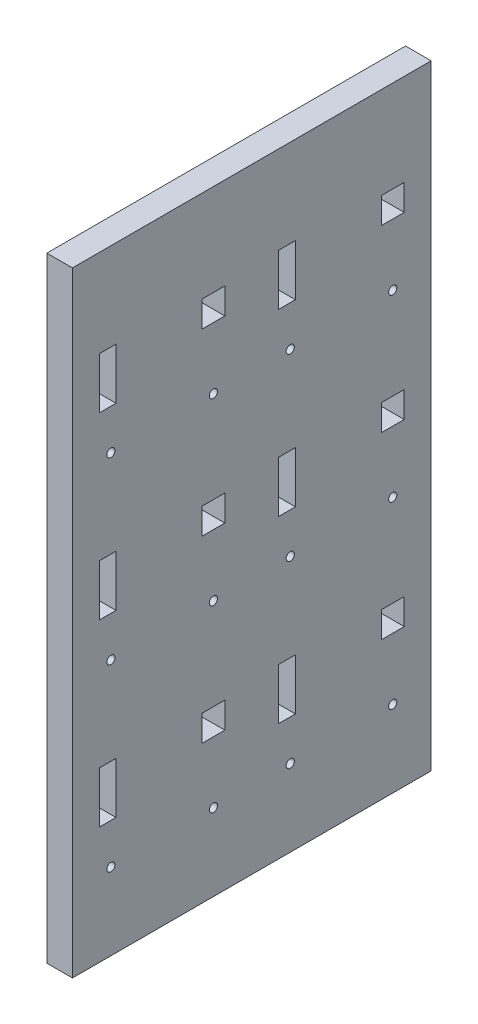
SolidWorks part; units mm, degrees
ref_plane "Alzado" through (0, 0, 0) normal (1, 0, 0) x (0, 1, 0)
ref_plane "Planta" through (0, 0, 0) normal (0, 0, 1) x (0, 1, 0)
ref_plane "Vista lateral" through (0, 0, 0) normal (0, 1, 0) x (-1, 0, 0)
sketch "Croquis2" plane through (0, 0, 0) normal (1, 0, 0) x (0, 1, 0)
  line L1 (0, 0) -> (240, 0)
  line L2 (0, 0) -> (0, 140)
  line L3 (0, 140) -> (240, 140)
  line L4 (240, 0) -> (240, 140)
  dimension "D1" = 240
  dimension "D2" = 140
extrude "Saliente-Extruir1" add sketch "Croquis2" along normal blind 10
sketch "Croquis3" plane through (10, 0, 0) normal (1, 0, 0) x (0, 1, 0)
  line L0 (240, 0) -> (240, 140) construction
  line L1 (0, 140) -> (0, 0) construction
  line L2 (0, 0) -> (240, 0) construction
  line L3 (240, 0) -> (240, 140) construction
  line L4 (0, 140) -> (0, 0) construction
  line L5 (0, 0) -> (240, 0)
  line L6 (85, 154.7761) -> (85, -24.7939) construction
  line L7 (155, 154.7761) -> (155, -26.7975) construction
  line L12 (15, 154.7761) -> (15, -24.7939) construction
  line L13 (225, 154.7761) -> (225, -26.7975) construction
  line L14 (155, -10.8706) -> (225, -10.8706) construction
  line L15 (120, -173.0582) -> (120, 151.3171) construction
  line L16 (15, -10.8706) -> (85, -10.8706) construction
  line L17 (85, -10.8706) -> (155, -10.8706) construction
  line L18 (190, -176.5172) -> (190, 154.7761) construction
  line L19 (-278.0925, 70) -> (278.0925, 70) construction
  line L20 (50, -173.0582) -> (50, 151.3171) construction
  line L21 (-19.3483, 125) -> (262.904, 125) construction
  line L22 (-19.3483, 85) -> (262.904, 85) construction
  line L23 (-19.3483, 55) -> (262.904, 55) construction
  line L24 (-19.3483, 15) -> (262.904, 15) construction
  line L25 (240, 140) -> (0, 140) construction
  line L26 (30, 134.2549) -> (30, 75.3306) construction
  line L27 (140.43, 129.5) -> (140.43, 123)
  line L28 (65.75, 129.5) -> (45.75, 129.5)
  line L29 (65.75, 129.5) -> (65.75, 123)
  line L30 (65.75, 123) -> (45.75, 123)
  line L31 (45.75, 129.5) -> (45.75, 123)
  line L32 (64.19, 89.48) -> (54.03, 89.48)
  line L33 (64.19, 89.48) -> (64.19, 80.52)
  line L34 (64.19, 80.52) -> (54.03, 80.52)
  line L35 (54.03, 89.48) -> (54.03, 80.52)
  line L36 (140.43, 129.5) -> (120.43, 129.5)
  line L37 (120.43, 129.5) -> (120.43, 123)
  line L38 (140.43, 123) -> (120.43, 123)
  line L39 (138.87, 89.48) -> (138.87, 80.52)
  line L40 (138.87, 89.48) -> (128.71, 89.48)
  line L41 (128.71, 89.48) -> (128.71, 80.52)
  line L42 (138.87, 80.52) -> (128.71, 80.52)
  line L43 (215.11, 129.5) -> (215.11, 123)
  line L44 (215.11, 129.5) -> (195.11, 129.5)
  line L45 (195.11, 129.5) -> (195.11, 123)
  line L46 (215.11, 123) -> (195.11, 123)
  line L47 (213.55, 89.48) -> (213.55, 80.52)
  line L48 (213.55, 89.48) -> (203.39, 89.48)
  line L49 (203.39, 89.48) -> (203.39, 80.52)
  line L50 (213.55, 80.52) -> (203.39, 80.52)
  line L51 (140.43, 59.5) -> (140.43, 53)
  line L52 (140.43, 59.5) -> (120.43, 59.5)
  line L53 (120.43, 59.5) -> (120.43, 53)
  line L54 (140.43, 53) -> (120.43, 53)
  line L55 (138.87, 19.48) -> (138.87, 10.52)
  line L56 (138.87, 19.48) -> (128.71, 19.48)
  line L57 (128.71, 19.48) -> (128.71, 10.52)
  line L58 (138.87, 10.52) -> (128.71, 10.52)
  line L59 (215.11, 59.5) -> (215.11, 53)
  line L60 (215.11, 59.5) -> (195.11, 59.5)
  line L61 (195.11, 59.5) -> (195.11, 53)
  line L62 (215.11, 53) -> (195.11, 53)
  line L63 (213.55, 19.48) -> (213.55, 10.52)
  line L64 (213.55, 19.48) -> (203.39, 19.48)
  line L65 (203.39, 19.48) -> (203.39, 10.52)
  line L66 (213.55, 10.52) -> (203.39, 10.52)
  line L67 (65.75, 59.5) -> (65.75, 53)
  line L68 (65.75, 59.5) -> (45.75, 59.5)
  line L69 (45.75, 59.5) -> (45.75, 53)
  line L70 (65.75, 53) -> (45.75, 53)
  line L71 (64.19, 19.48) -> (64.19, 10.52)
  line L72 (64.19, 19.48) -> (54.03, 19.48)
  line L73 (54.03, 19.48) -> (54.03, 10.52)
  line L74 (64.19, 10.52) -> (54.03, 10.52)
  circle A2 centre (30, 125) radius 1.6
  circle A3 centre (30, 85) radius 1.6
  circle A4 centre (70, 85) radius 1.6
  circle A6 centre (100, 85) radius 1.6
  circle A7 centre (100, 125) radius 1.6
  circle A8 centre (140, 85) radius 1.6
  circle A10 centre (170, 85) radius 1.6
  circle A11 centre (210, 85) radius 1.6
  circle A12 centre (210, 125) radius 1.6
  circle A13 centre (170, 125) radius 1.6
  circle A14 centre (210, 55) radius 1.6
  circle A15 centre (210, 15) radius 1.6
  circle A16 centre (170, 55) radius 1.6
  circle A17 centre (170, 15) radius 1.6
  circle A18 centre (140, 15) radius 1.6
  circle A19 centre (140, 55) radius 1.6
  circle A20 centre (100, 55) radius 1.6
  circle A21 centre (100, 15) radius 1.6
  circle A22 centre (70, 15) radius 1.6
  circle A24 centre (30, 55) radius 1.6
  circle A25 centre (30, 15) radius 1.6
  point P19 (120, -10.8706)
  point P22 (190, -10.8706)
  point P25 (50, -10.8706)
  point P28 (0, 70)
  dimension "D9" = 20
  dimension "D10" = 3.2
  dimension "D1" = 15
  dimension "D2" = 15
  dimension "D3" = 70
  dimension "D4" = 70
  dimension "D5" = 40
  dimension "D6" = 40
  dimension "D7" = 15
  dimension "D8" = 15
  dimension "D11" = 15.75
  dimension "D12" = 20
  dimension "D13" = 4.48
  dimension "D14" = 10.16
  dimension "D15" = 5.81
  dimension "D16" = 4.48
  dimension "D19" = 2
  dimension "D20" = 2
  dimension "D17" = 3
  dimension "D18" = 2
extrude "Cortar-Extruir1" cut sketch "Croquis3" against normal through all both and the other way through all contours L28 L31 L30 L29 | L32 L35 L34 L33 | A2 | A3 region at (10, 55.75, 126.25) region at (10, 59.11, 85)
pattern_linear "MatrizL1" count 3 spacing 70 along (0, 1, 0) count 2 spacing 70 along (0, 0, -1) of "Cortar-Extruir1"
